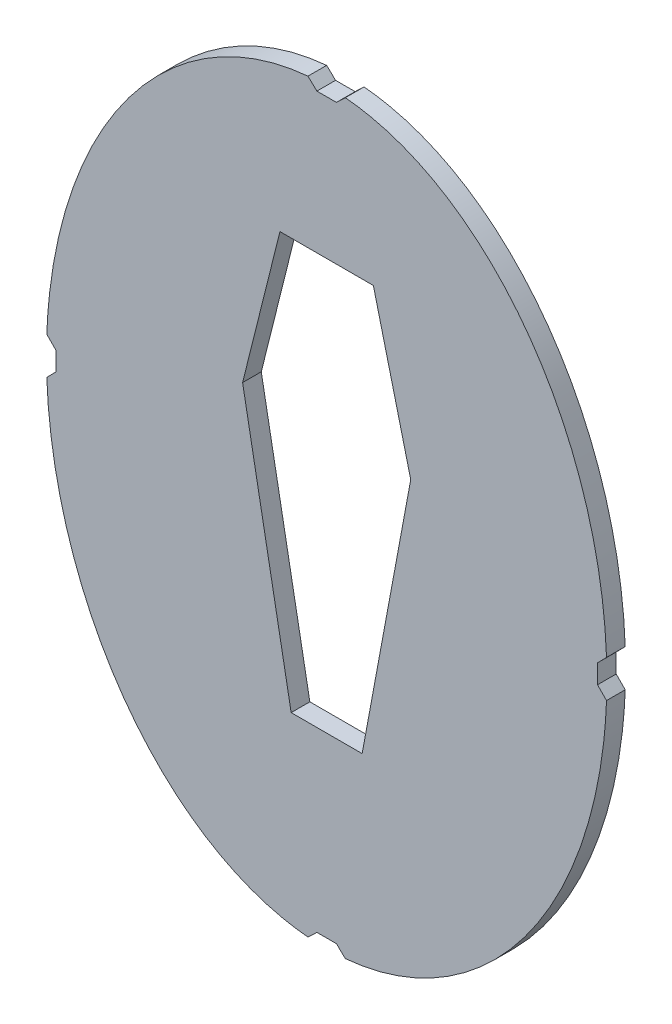
SolidWorks part; units mm, degrees
ref_plane "정면" through (0, 0, 0) normal (0, 0, 1) x (1, 0, 0)
ref_plane "윗면" through (0, 0, 0) normal (0, 1, 0) x (1, 0, 0)
ref_plane "우측면" through (0, 0, 0) normal (1, 0, 0) x (0, 0, -1)
sketch "스케치1" plane through (0, 0, 0) normal (0, 0, 1) x (1, 0, 0)
  ellipse E0 centre (0, 0) end of major axis (0, -20) minor radius 15
  dimension "D1" = 40
  dimension "D2" = 30
extrude "보스-돌출1" add sketch "스케치1" along normal blind 1
sketch "스케치2" plane through (0, 0, 1) normal (0, 0, 1) x (1, 0, 0)
  line L0 (2.5, 12) -> (-2.5, 12)
  line L1 (-2.5, 12) -> (-4.5, 4)
  line L2 (0, 12) -> (0, -4.5732) construction
  line L4 (2.5, 12) -> (4.5, 4)
  line L5 (-1.9, -10) -> (-4.5, 4)
  line L6 (-1.9, -10) -> (1.9, -10)
  line L7 (1.9, -10) -> (4.5, 4)
  point P6 (-3.304, -12.9195)
  point P11 (0, -10)
  dimension "D1" = 3.8
  dimension "D2" = 5
  dimension "D3" = 22
  dimension "D4" = 9
  dimension "D5" = 14
  dimension "D6" = 10
extrude "컷-돌출1" cut sketch "스케치2" against normal blind 1
sketch "스케치3" plane through (0, 0, 1) normal (0, 0, 1) x (1, 0, 0)
  line L1 (-0.5, 20.5) -> (0.5, 20.5)
  line L2 (-0.5, 20.5) -> (-0.5, 19.5)
  line L3 (-0.5, 19.5) -> (0.5, 19.5)
  line L4 (0.5, 20.5) -> (0.5, 19.5)
  line L5 (-0.5, 20.5) -> (0.5, 19.5) construction
  line L6 (-0.5, 19.5) -> (0.5, 20.5) construction
  line L7 (14.5, 0.5) -> (15.5, 0.5)
  line L8 (14.5, 0.5) -> (14.5, -0.5)
  line L9 (14.5, -0.5) -> (15.5, -0.5)
  line L10 (15.5, 0.5) -> (15.5, -0.5)
  line L11 (14.5, 0.5) -> (15.5, -0.5) construction
  line L12 (14.5, -0.5) -> (15.5, 0.5) construction
  line L13 (-15.5, 0.5) -> (-14.5, 0.5)
  line L14 (-15.5, 0.5) -> (-15.5, -0.5)
  line L15 (-15.5, -0.5) -> (-14.5, -0.5)
  line L16 (-14.5, 0.5) -> (-14.5, -0.5)
  line L17 (-15.5, 0.5) -> (-14.5, -0.5) construction
  line L18 (-15.5, -0.5) -> (-14.5, 0.5) construction
  line L19 (-0.5, -19.5) -> (0.5, -19.5)
  line L20 (-0.5, -19.5) -> (-0.5, -20.5)
  line L21 (-0.5, -20.5) -> (0.5, -20.5)
  line L22 (0.5, -19.5) -> (0.5, -20.5)
  line L23 (-0.5, -19.5) -> (0.5, -20.5) construction
  line L24 (-0.5, -20.5) -> (0.5, -19.5) construction
  ellipse E0 centre (0, 0) end of major axis (0, -20) minor radius 15 construction
  point P0 (0, 20)
  point P11 (15, 0)
  point P16 (-15, 0)
  point P21 (0, -20)
  dimension "D1" = 1
  dimension "D2" = 1
  dimension "D3" = 1
  dimension "D4" = 1
  dimension "D5" = 1
  dimension "D6" = 1
  dimension "D7" = 1
  dimension "D8" = 1
extrude "컷-돌출2" cut sketch "스케치3" against normal blind 1
chamfer "모따기1" distance 0.5 angle 45 8 edges at (0.5, -19.9889, 0.5) (-0.5, -19.9889, 0.5) (-14.9953, 0.5, 0.5) (-14.9953, -0.5, 0.5) (-0.5, 19.9889, 0.5) (0.5, 19.9889, 0.5) (14.9953, -0.5, 0.5) (14.9953, 0.5, 0.5) first distance on face at (0.5, -19.7444, 0.5) first distance on face at (-0.5, -19.7444, 0.5) first distance on face at (-14.7477, 0.5, 0.5) first distance on face at (-14.7477, -0.5, 0.5) first distance on face at (-0.5, 19.7444, 0.5) first distance on face at (0.5, 19.7444, 0.5) first distance on face at (14.7477, -0.5, 0.5) first distance on face at (14.7477, 0.5, 0.5)
